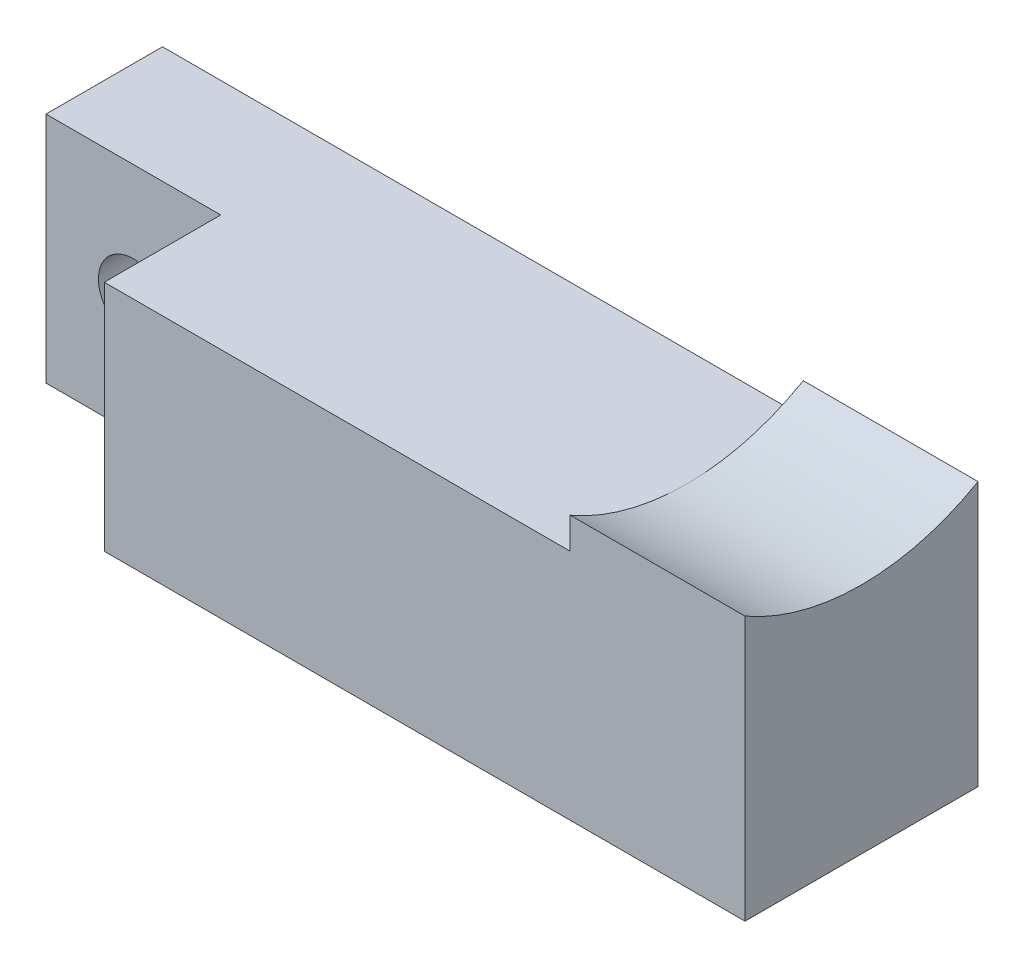
SolidWorks part; units mm, degrees
ref_plane "Alzado" through (0, 0, 0) normal (0, 0, 1) x (1, 0, 0)
ref_plane "Planta" through (0, 0, 0) normal (0, 1, 0) x (1, 0, 0)
ref_plane "Vista lateral" through (0, 0, 0) normal (1, 0, 0) x (0, 0, -1)
sketch "Croquis2" plane through (0, 0, 0) normal (0, 1, 0) x (1, 0, 0)
  line L1 (0, 0) -> (70, 0)
  line L2 (0, 0) -> (0, 20)
  line L3 (0, 20) -> (70, 20)
  line L4 (70, 0) -> (70, 20)
  dimension "D1" = 20
  dimension "D2" = 70
extrude "Saliente-Extruir1" add sketch "Croquis2" along normal blind 20 contours L2 L3 L4 L1
sketch "Croquis3" plane through (0, 0, 0) normal (0, 1, 0) x (1, 0, 0)
  line L1 (0, 0) -> (15, 0)
  line L2 (0, 0) -> (0, 10)
  line L3 (0, 10) -> (15, 10)
  line L4 (15, 0) -> (15, 10)
  dimension "D1" = 15
  dimension "D2" = 10
extrude "Cortar-Extruir3" cut sketch "Croquis3" against normal through all and the other way through all contours L2 L3 L4 L1
sketch "Croquis4" plane through (0, 0, 0) normal (0, 1, 0) x (1, 0, 0)
  line L0 (70, 0) -> (70, 20) construction
  line L1 (0, 20) -> (70, 20) construction
  circle A0 centre (24, 10) radius 2
  dimension "D1" = 4
  dimension "D2" = 46
  dimension "D3" = 10
extrude "Cortar-Extruir6" cut sketch "Croquis4" against normal blind 6 and the other way blind 6 contours A0
thread "Rosca1" pitch 0.7 method cut profile "Perfil de rosca2" start angle 0, offset 1, length 6, pitch 0.7, diameter 4
ref_plane "Plano4" through (22, 7, -10) normal (0, 0, 1) x (-1, 0, 0)
sketch "Perfil de rosca2" plane through (22, 7, -10) normal (0, 0, 1) x (-1, 0, 0)
  line L0 (0, 0) -> (0, 0.7) construction
  line L1 (0, 0) -> (0.3789, 0.2187)
  line L2 (0.3789, 0.2187) -> (0.3789, 0.3062)
  line L3 (0.3789, 0.3062) -> (0, 0.525)
  line L4 (0.3789, 0.2625) -> (0, 0.2625) construction
  line L11 (0, 0) -> (0, 0.525)
  point P2 (0, 0)
  dimension "Pitch" = 0.7
  dimension "Profile_Angle" = 60
  dimension "Profile_Land" = 0.0875
  dimension "Profile_Height" = 0.3789
sketch "Croquis12" plane through (0, 0, 0) normal (0, 0, 1) x (1, 0, 0)
  line L0 (0, 0) -> (15, 0) construction
  line L1 (0, 0) -> (0, 20) construction
  circle A0 centre (7.5, 10) radius 3
  dimension "D1" = 6
  dimension "D2" = 10
  dimension "D3" = 7.5
extrude "Cortar-Extruir7" cut sketch "Croquis12" against normal through all contours A0
sketch "Croquis13" plane through (0, 20, 0) normal (0, 1, 0) x (1, 0, 0)
  line L0 (0, 20) -> (70, 20) construction
  line L1 (70, 0) -> (55, 0)
  line L2 (70, 0) -> (70, 20)
  line L3 (70, 20) -> (55, 20)
  line L4 (55, 0) -> (55, 20)
  dimension "D1" = 15
extrude "Saliente-Extruir2" add sketch "Croquis13" along normal blind 2.6795
sketch "Croquis14" plane through (55, 0, 0) normal (-1, 0, 0) x (0, 0, 1)
  line L0 (-20, 22.6795) -> (0, 22.6795) construction
  arc A0 (-20, 22.6795) -> (0, 22.6795) centre (-10, 40) ccw
  point P3 (0, 0)
extrude "Cortar-Extruir8" cut sketch "Croquis14" against normal through all and the other way through all contours A0
